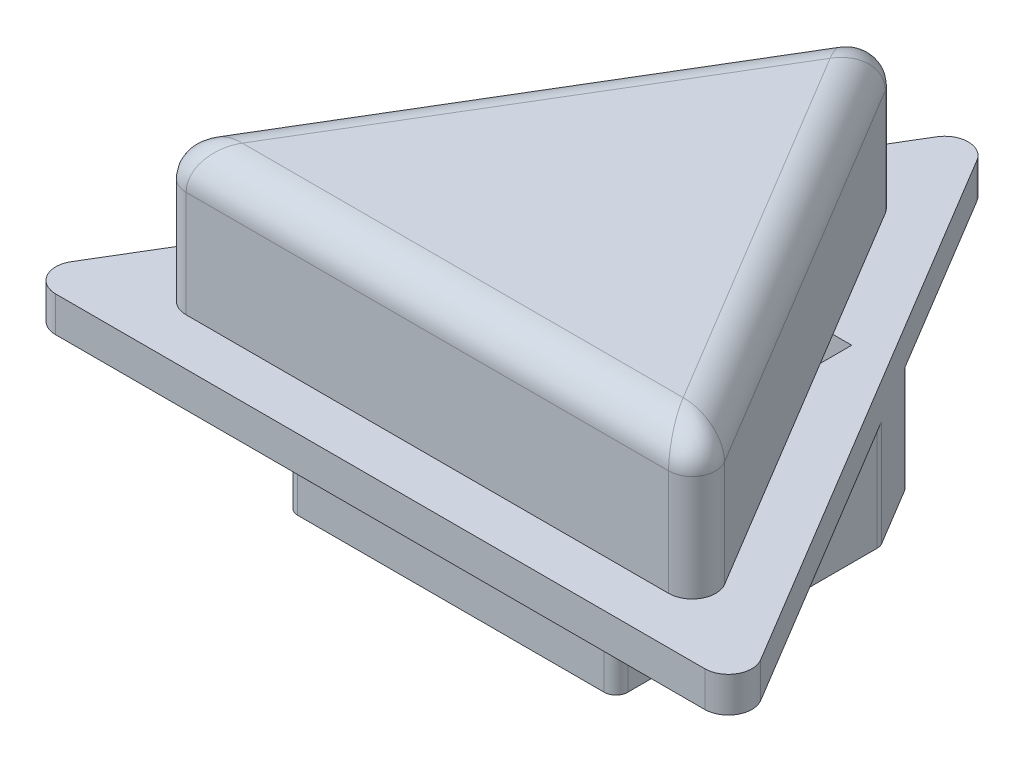
SolidWorks part; units mm, degrees
ref_plane "Front Plane" through (0, 0, 0) normal (0, 0, 1) x (1, 0, 0)
ref_plane "Top Plane" through (0, 0, 0) normal (0, 1, 0) x (1, 0, 0)
ref_plane "Right Plane" through (0, 0, 0) normal (1, 0, 0) x (0, 0, -1)
sketch "Sketch1" plane through (0, 0, 0) normal (0, 1, 0) x (1, 0, 0)
  line L0 (0, 0) -> (6, 10)
  line L1 (6, 10) -> (12, 0)
  line L2 (12, 0) -> (0, 0)
  point P3 (6, 0)
  dimension "D1" = 12
  dimension "D2" = 10
extrude "Boss-Extrude1" add sketch "Sketch1" along normal blind 3
sketch "Sketch2" plane through (0, 0, 0) normal (0, -1, 0) x (1, 0, 0)
  line L12 (13.7662, 1) -> (-1.7662, 1)
  line L13 (-1.7662, 1) -> (6, -11.9437)
  line L14 (6, -11.9437) -> (13.7662, 1)
  line L15 (13.7662, 1) -> (-1.7662, 1)
  line L16 (-1.7662, 1) -> (6, -11.9437)
  line L17 (6, -11.9437) -> (13.7662, 1)
  dimension "D1" = 1
extrude "Boss-Extrude2" add sketch "Sketch2" along normal blind 0.75
sketch "Sketch3" plane through (0, -0.75, 0) normal (0, -1, 0) x (1, 0, 0)
  line L0 (13.7662, 1) -> (-1.7662, 1) construction
  line L1 (8.5, -1.5) -> (3.5, -1.5)
  line L2 (8.5, -1.5) -> (8.5, -6.5)
  line L3 (8.5, -6.5) -> (3.5, -6.5)
  line L4 (3.5, -1.5) -> (3.5, -6.5)
  line L5 (8.5, -1.5) -> (3.5, -6.5) construction
  line L6 (8.5, -6.5) -> (3.5, -1.5) construction
  line L7 (9.5, -7.5) -> (2.5, -7.5)
  line L8 (2.5, -0.5) -> (2.5, -7.5)
  line L9 (9.5, -0.5) -> (2.5, -0.5)
  line L10 (9.5, -0.5) -> (9.5, -7.5)
  line L11 (-1.7662, 1) -> (6, -11.9437) construction
  line L12 (6, -11.9437) -> (13.7662, 1) construction
  line L13 (-1.7662, 1) -> (6, -11.9437)
  line L14 (6, -11.9437) -> (13.7662, 1)
  point P0 (6, -4)
  point P8 (6, 1)
  line M1 (6, -11.9437) -> (13.7662, 1)
  line M3 (-1.7662, 1) -> (6, -11.9437)
  dimension "D1" = 5
  dimension "D2" = 5
  dimension "D4" = 5
  dimension "D3" = 1
extrude "Boss-Extrude3" add sketch "Sketch3" along normal blind 2.25 contours L10 L9 L8 L7 L4 L1 L2 L3 M3 M1 region at (6, -0.75, -7.401)
fillet "Fillet1" radius 0.5 3 edges at (6, -0.375, -11.9437) (-1.7662, -0.375, 1) (13.7662, -0.375, 1)
fillet "Fillet2" radius 0.5 3 edges at (0, 1.5, 0) (12, 1.5, 0) (6, 1.5, -10)
fillet "Fillet4" radius 0.75 6 edges at (6, 3, -9.5282) (8.9872, 3, -5.0213) (11.552, 3, -0.2537) (6, 3, 0) (0.448, 3, -0.2537) (3.0128, 3, -5.0213)
fillet "Fillet6" radius 0.25 6 edges at (2.5, -1.875, -0.5) (2.5, -1.875, -6.1103) (3.3338, -1.875, -7.5) (8.6662, -1.875, -7.5) (9.5, -1.875, -6.1103) (9.5, -1.875, -0.5)
sketch "Sketch4" plane through (0, -0.75, 0) normal (0, -1, 0) x (1, 0, 0)
  line L4 (8.5, -1.5) -> (3.5, -1.5)
  line L5 (3.5, -1.5) -> (3.5, -6.5)
  line L6 (3.5, -6.5) -> (8.5, -6.5)
  line L7 (8.5, -6.5) -> (8.5, -1.5)
  line L8 (8.5, -1.5) -> (3.5, -1.5)
  line L9 (3.5, -1.5) -> (3.5, -6.5)
  line L10 (3.5, -6.5) -> (8.5, -6.5)
  line L11 (8.5, -6.5) -> (8.5, -1.5)
  dimension "D1" = 0
extrude "Cut-Extrude1" cut sketch "Sketch4" against normal blind 0.75
